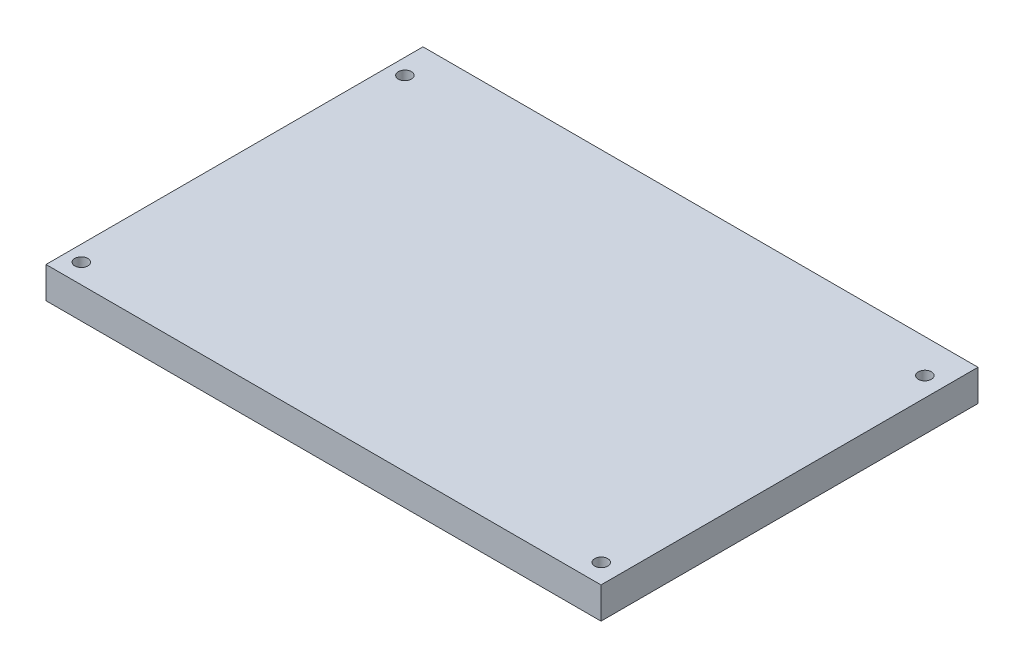
SolidWorks part; units mm, degrees
ref_plane "Front Plane" through (0, 0, 0) normal (0, 0, 1) x (1, 0, 0)
ref_plane "Top Plane" through (0, 0, 0) normal (0, 1, 0) x (1, 0, 0)
ref_plane "Right Plane" through (0, 0, 0) normal (1, 0, 0) x (0, 0, -1)
sketch "Sketch2" plane through (0, 0, 0) normal (0, 0, 1) x (1, 0, 0)
  line L1 (-53, 3) -> (53, 3)
  line L2 (-53, 3) -> (-53, -3)
  line L3 (-53, -3) -> (53, -3)
  line L4 (53, 3) -> (53, -3)
  line L5 (-53, 3) -> (53, -3) construction
  line L6 (-53, -3) -> (53, 3) construction
  point P0 (0, 0)
  dimension "D1" = 106
  dimension "D2" = 6
extrude "Boss-Extrude1" add sketch "Sketch2" along normal blind 72
sketch "Sketch4" plane through (0, 3, 0) normal (0, 1, 0) x (1, 0, 0)
  line L0 (-53, -72) -> (53, -72) construction
  line L1 (53, -72) -> (53, 0) construction
  line L2 (-62.6793, -72) -> (-62.6793, -4) construction
  line L3 (-50.0049, -4) -> (-53, -4) construction
  line L4 (-53, -72) -> (-53, 0) construction
  line L5 (-53, -4) -> (53, -4) construction
  line L6 (-56.8726, -4) -> (-56.8726, -6.4507) construction
  line L7 (-55.3882, -72) -> (-55.3882, -68.2507) construction
  line L8 (53, -77.5021) -> (49.2951, -77.5021) construction
  line L9 (53, 3.1613) -> (49.2951, 3.1613) construction
  line L10 (-53.7098, 3.1613) -> (-50.0049, 3.1613) construction
  line L11 (-53, -36) -> (53, -36) construction
  line L12 (0, 0) -> (0, -72) construction
  line L13 (53, 0) -> (-53, 0) construction
  circle A0 centre (-50.0049, -68.2507) radius 1.25
  circle A1 centre (49.2951, -68.2507) radius 1.25
  circle A2 centre (49.2951, -6.4507) radius 1.25
  circle A3 centre (-50.0049, -6.4507) radius 1.25
  dimension "D6" = 2.5
  dimension "D1" = 106
  dimension "D2" = 72
  dimension "D3" = 68
  dimension "D4" = 99.3
  dimension "D5" = 61.8
extrude "Cut-Extrude1" cut sketch "Sketch4" against normal through all contours A3 | A0 | A1 | A2 region at (-50.0049, 3, 68.2507) region at (49.2951, 3, 68.2507) region at (49.2951, 3, 6.4507) region at (-50.0049, 3, 6.4507)
sketch "Sketch5" plane through (0, 0, 0) normal (0, 0, -1) x (-1, 0, 0)
  line L0 (-53, 0) -> (53, 0) construction
  line L1 (-53, -3) -> (-53, 3) construction
  line L2 (53, 3) -> (53, -3) construction
  circle A0 centre (0, 0) radius 1.75
  circle A1 centre (26.5, 0) radius 1.75
  circle A2 centre (-26.5, 0) radius 1.75
  point P12 (0, 0)
  dimension "D3" = 3.5
  dimension "D1" = 26.5
  dimension "D2" = 26.5
extrude "Cut-Extrude2" cut sketch "Sketch5" against normal blind 10
